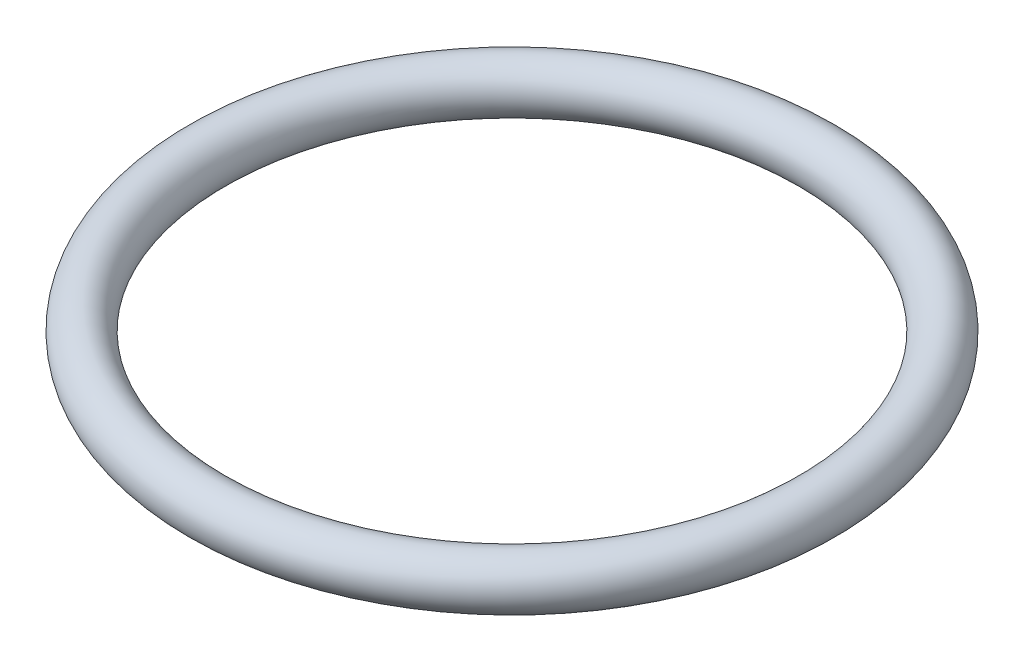
SolidWorks part; units mm, degrees
material "POLYURETHANE (11671)"
ref_plane "Front Plane" through (0, 0, 0) normal (0, 0, 1) x (1, 0, 0)
ref_plane "Top Plane" through (0, 0, 0) normal (0, 1, 0) x (1, 0, 0)
ref_plane "Right Plane" through (0, 0, 0) normal (1, 0, 0) x (0, 0, -1)
sketch "Sketch1" plane through (0, 0, 0) normal (0, 0, 1) x (1, 0, 0)
  line L0 (30.25, 0) -> (-30.25, 0) construction
  line L1 (0, 0) -> (0, 12.7) construction
  circle A0 centre (-30.25, 0) radius 2.5
  point P3 (-32.75, 0)
  point P4 (0, 0)
  dimension "D2" = 5
  dimension "D1" = 12.7
  dimension "D3" = 65.5
revolve "Revolve1" add sketch "Sketch1" angle 360 about L1
ref_axis "Axis1" through (0, 13.46, 0) along (0, -1, 0)
